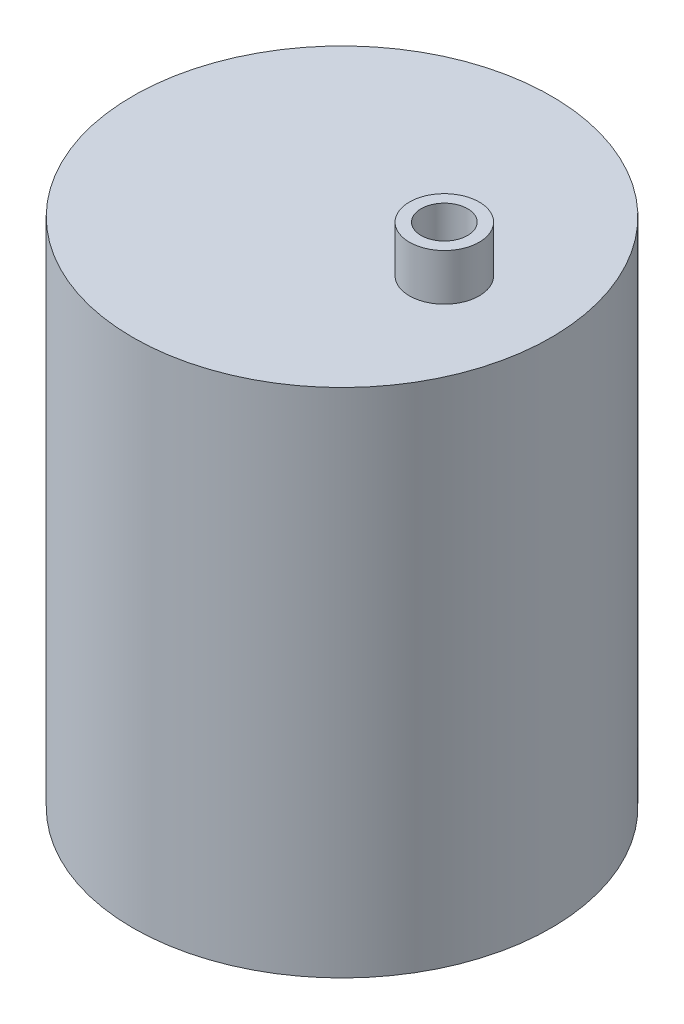
SolidWorks part; units mm, degrees
note: The reader was unsure of these and kept them because the rebuilt part matched: shared geometry of "Sketch2<3>", "Sketch2<4>", "Sketch3<2>", "Sketch2<5>".
ref_plane "Front Plane" through (0, 0, 0) normal (0, 0, 1) x (1, 0, 0)
ref_plane "Top Plane" through (0, 0, 0) normal (0, 1, 0) x (1, 0, 0)
ref_plane "Right Plane" through (0, 0, 0) normal (1, 0, 0) x (0, 0, -1)
sketch "Sketch1" plane through (0, 0, 0) normal (1, 0, 0) x (0, 0, -1)
  line L0 (0, 0) -> (0, -39311.353) construction
  line L4 (27, -10.4615) -> (35, -10.4615)
  line L6 (35, 89.5385) -> (45, 89.5385)
  line L7 (45, 89.5385) -> (45, -20.4615)
  line L8 (45, -20.4615) -> (0, -20.4615)
  line L9 (0, -20.4615) -> (0, -10.4615)
  line L11 (0, 49.5385) -> (0, -10.4615)
  line L12 (0, -10.4615) -> (8, -10.4615) construction
  line L13 (0, 49.5385) -> (8, 49.5385)
  line L14 (8, 49.5385) -> (27, -10.4615)
  line L15 (8, 49.5385) -> (8, -10.4615) construction
  line L16 (8, -10.4615) -> (27, -10.4615) construction
  line L17 (35, -10.4615) -> (35, 79.5385)
  line L18 (0, 79.5385) -> (0, 89.5385)
  line L19 (35, 79.5385) -> (35, 89.5385)
  line L20 (0, 89.5385) -> (35, 89.5385)
  line L21 (35, 79.5385) -> (0, 79.5385)
  dimension "D1" = 10
  dimension "D2" = 8
  dimension "D3" = 110
  dimension "D4" = 60
  dimension "D5" = 8
  dimension "D6" = 45
revolve "Revolve1" add sketch "Sketch1" angle 360 about L0
sketch "Sketch2" plane through (0, -20.4615, 0) normal (0, -1, 0) x (1, 0, 0)
  line L0 (5.5902, 5) -> (40, 5)
  line L1 (0, 0) -> (0, 5)
  line L2 (40, 5) -> (40, -5)
  line L3 (40, -5) -> (5.5902, -5)
  line L4 (-5, -40) -> (-5, -5.5902)
  line L5 (5, -5.5902) -> (5, -40)
  line L6 (5, -40) -> (-5, -40)
  line L7 (-40, 5) -> (-5.5902, 5)
  line L8 (-5.5902, -5) -> (-40, -5)
  line L9 (-40, -5) -> (-40, 5)
  line L10 (5, 40) -> (5, 5.5902)
  line L11 (-5, 5.5902) -> (-5, 40)
  line L12 (-5, 40) -> (5, 40)
  line L13 (11.1663, 2.7503) -> (22.5, 1)
  line L14 (22.5, 1) -> (22.5, 0)
  line L15 (7.5, 0) -> (22.5, 0) construction
  line L16 (22.5, 0) -> (22.5, -1)
  line L17 (22.5, -1) -> (11.1663, -2.7503)
  line L18 (11.1663, 2.7503) -> (11.1663, -2.7503) construction
  line L19 (5.3033, -5.3033) -> (15.9099, -15.9099) construction
  line L20 (9.8405, -5.951) -> (16.617, -15.2028)
  line L21 (15.2028, -16.617) -> (5.951, -9.8405)
  line L22 (9.8405, -5.951) -> (5.951, -9.8405) construction
  line L23 (16.617, -15.2028) -> (15.9099, -15.9099)
  line L24 (15.9099, -15.9099) -> (15.2028, -16.617)
  line L25 (0, -7.5) -> (0, -22.5) construction
  line L26 (2.7503, -11.1663) -> (1, -22.5)
  line L27 (-1, -22.5) -> (-2.7503, -11.1663)
  line L28 (2.7503, -11.1663) -> (-2.7503, -11.1663) construction
  line L29 (1, -22.5) -> (0, -22.5)
  line L30 (0, -22.5) -> (-1, -22.5)
  line L31 (-5.3033, -5.3033) -> (-15.9099, -15.9099) construction
  line L32 (-5.951, -9.8405) -> (-15.2028, -16.617)
  line L33 (-16.617, -15.2028) -> (-9.8405, -5.951)
  line L34 (-5.951, -9.8405) -> (-9.8405, -5.951) construction
  line L35 (-15.2028, -16.617) -> (-15.9099, -15.9099)
  line L36 (-15.9099, -15.9099) -> (-16.617, -15.2028)
  line L37 (-7.5, 0) -> (-22.5, 0) construction
  line L38 (-11.1663, -2.7503) -> (-22.5, -1)
  line L39 (-22.5, 1) -> (-11.1663, 2.7503)
  line L40 (-11.1663, -2.7503) -> (-11.1663, 2.7503) construction
  line L41 (-22.5, -1) -> (-22.5, 0)
  line L42 (-22.5, 0) -> (-22.5, 1)
  line L43 (-5.3033, 5.3033) -> (-15.9099, 15.9099) construction
  line L44 (-9.8405, 5.951) -> (-16.617, 15.2028)
  line L45 (-15.2028, 16.617) -> (-5.951, 9.8405)
  line L46 (-9.8405, 5.951) -> (-5.951, 9.8405) construction
  line L47 (-16.617, 15.2028) -> (-15.9099, 15.9099)
  line L48 (-15.9099, 15.9099) -> (-15.2028, 16.617)
  line L49 (0, 7.5) -> (0, 22.5) construction
  line L50 (-2.7503, 11.1663) -> (-1, 22.5)
  line L51 (1, 22.5) -> (2.7503, 11.1663)
  line L52 (-2.7503, 11.1663) -> (2.7503, 11.1663) construction
  line L53 (-1, 22.5) -> (0, 22.5)
  line L54 (0, 22.5) -> (1, 22.5)
  line L55 (5.3033, 5.3033) -> (15.9099, 15.9099) construction
  line L56 (5.951, 9.8405) -> (15.2028, 16.617)
  line L57 (16.617, 15.2028) -> (9.8405, 5.951)
  line L58 (5.951, 9.8405) -> (9.8405, 5.951) construction
  line L59 (15.2028, 16.617) -> (15.9099, 15.9099)
  line L60 (15.9099, 15.9099) -> (16.617, 15.2028)
  circle A0 centre (0, 0) radius 5
  circle A2 centre (0, 0) radius 7.5
  circle A3 centre (0, 0) radius 11.5
  point P24 (0, 0)
  point P73 (0, 0)
  dimension "D1" = 10
  dimension "D2" = 15
  dimension "D4" = 4
  dimension "D8" = 23
  dimension "D9" = 8
  dimension "D3" = 40
  dimension "D5" = 15
  dimension "D6" = 10
  dimension "D7" = 2
extrude "Boss-Extrude1" add sketch "Sketch2" against normal blind 70 contours A2 L3 L2 L0 | A2 L7 L9 L8 | A2 L4 L6 L5 | A2 L10 L12 L11
extrude "Boss-Extrude2" add sketch "Sketch2<3>" along normal blind 10 contours A2 A0
sketch "Sketch2<3>" plane through (0, -20.4615, 0) normal (0, -1, 0) x (1, 0, 0) same geometry as "Sketch2"
extrude "Cut-Extrude1" cut sketch "Sketch2<4>" against normal blind 70
sketch "Sketch2<4>" plane through (0, -20.4615, 0) normal (0, -1, 0) x (1, 0, 0) same geometry as "Sketch2"
sketch "Sketch3" plane through (0, 89.5385, 0) normal (0, 1, 0) x (1, 0, 0)
  line L0 (0, 0) -> (22, 0) construction
  circle A0 centre (22, 0) radius 5
  circle A1 centre (22, 0) radius 7.5
  dimension "D1" = 22
  dimension "D2" = 10
  dimension "D3" = 15
extrude "Boss-Extrude3" add sketch "Sketch3" along normal blind 10
extrude "Cut-Extrude3" cut sketch "Sketch3<2>" against normal blind 10
sketch "Sketch3<2>" plane through (0, 89.5385, 0) normal (0, 1, 0) x (1, 0, 0) same geometry as "Sketch3"
extrude "Boss-Extrude6" add sketch "Sketch2<5>" along normal blind 6 contours A3 L45 L48 L47 L44 | A3 L51 L54 L53 L50 | A3 L57 L60 L59 L56 | A3 L17 L16 L14 L13 | A3 L21 L24 L23 L20 | A3 L27 L30 L29 L26 | A3 L33 L36 L35 L32 | A3 L39 L42 L41 L38
sketch "Sketch2<5>" plane through (0, -20.4615, 0) normal (0, -1, 0) x (1, 0, 0) same geometry as "Sketch2"
